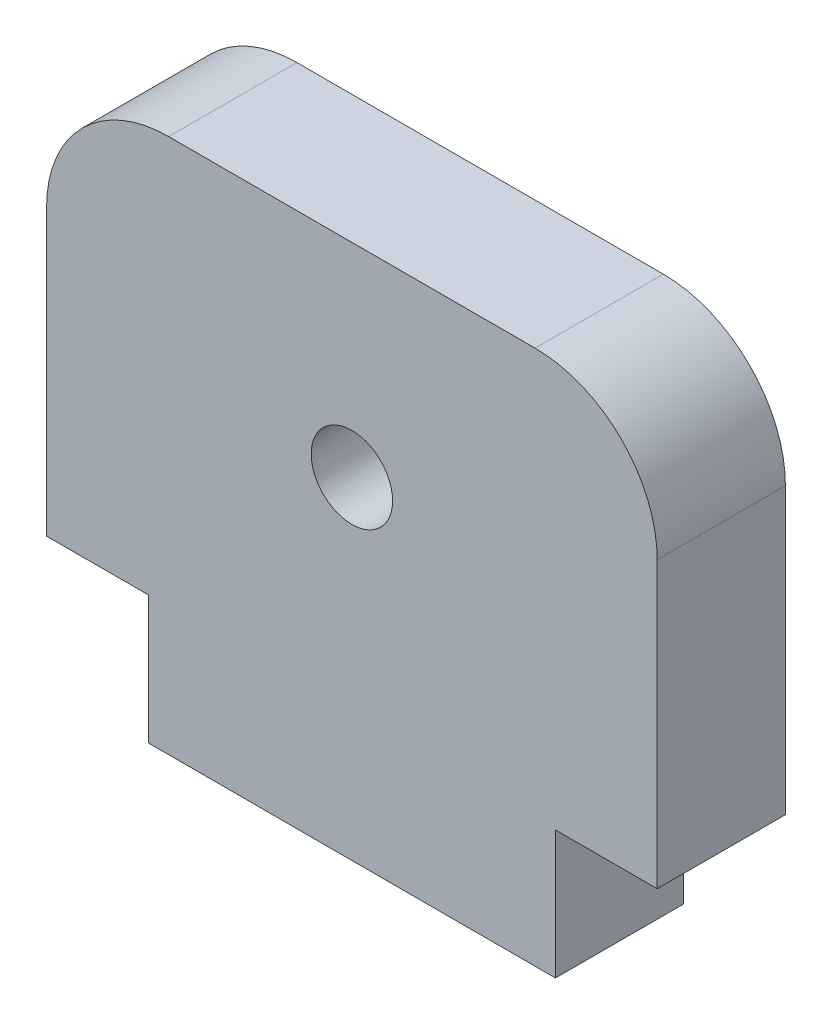
SolidWorks part; units mm, degrees
material "Hexcel AS4C (3000 Filaments)"
ref_plane "Front Plane" through (0, 0, 0) normal (0, 0, 1) x (1, 0, 0)
ref_plane "Top Plane" through (0, 0, 0) normal (0, 1, 0) x (1, 0, 0)
ref_plane "Right Plane" through (0, 0, 0) normal (1, 0, 0) x (0, 0, -1)
sketch "Sketch2" plane through (0, 0, 0) normal (0, 0, 1) x (1, 0, 0)
  line L0 (-9.525, -6.35) -> (-6.35, -6.35)
  line L1 (-9.525, -6.35) -> (9.525, -6.35) construction
  line L2 (-9.525, -6.35) -> (-9.525, 2.54)
  line L3 (-5.715, 6.35) -> (5.715, 6.35)
  line L4 (9.525, -6.35) -> (9.525, 2.54)
  line L5 (-9.525, -6.35) -> (9.525, 6.35) construction
  line L6 (-9.525, 6.35) -> (9.525, -6.35) construction
  line L7 (-6.35, -6.35) -> (-6.35, -10.35)
  line L8 (-6.35, -10.35) -> (6.35, -10.35)
  line L9 (6.35, -10.35) -> (6.35, -6.35)
  line L10 (6.35, -6.35) -> (9.525, -6.35)
  circle A0 centre (0, 0) radius 1.27
  arc A1 (5.715, 6.35) -> (9.525, 2.54) centre (5.715, 2.54) cw
  arc A2 (-9.525, 2.54) -> (-5.715, 6.35) centre (-5.715, 2.54) cw
  point P0 (0, 0)
  dimension "D3" = 2.54
  dimension "D6" = 3.81
  dimension "D1" = 12.7
  dimension "D2" = 19.05
  dimension "D4" = 4
  dimension "D5" = 12.7
extrude "Boss-Extrude1" add sketch "Sketch2" along normal blind 4
